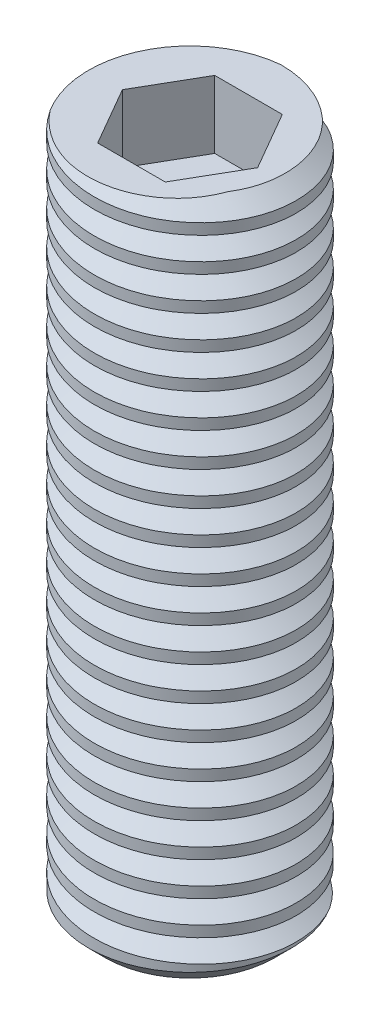
SolidWorks part; units mm, degrees
ref_plane "Alzado" through (0, 0, 0) normal (0, 0, 1) x (1, 0, 0)
ref_plane "Planta" through (0, 0, 0) normal (0, 1, 0) x (1, 0, 0)
ref_plane "Vista lateral" through (0, 0, 0) normal (1, 0, 0) x (0, 0, -1)
sketch "Croquis1" plane through (0, 0, 0) normal (0, 1, 0) x (1, 0, 0)
  circle A0 centre (0, 0) radius 1.5
  dimension "D1" = 3
extrude "Extruir1" add sketch "Croquis1" along normal blind 10
sketch "Croquis2" plane through (0, 0, 0) normal (0, 1, 0) x (1, 0, 0)
  circle A0 centre (0, 0) radius 1.5
  dimension "D1" = 3
curve "Hélice/Espiral1" pitch 0.5 height 21.5 turns 43
sketch "Croquis3" plane through (0, 0, 0) normal (1, 0, 0) x (0, 0, -1)
  line L0 (1.207, 0.3391) -> (1.64, 0.0891)
  line L1 (1.64, 0.0891) -> (1.7735, 0.0891)
  line L2 (1.7735, 0.0891) -> (1.7735, 0.5891)
  line L3 (1.7735, 0.5891) -> (1.64, 0.5891)
  line L4 (1.64, 0.5891) -> (1.207, 0.3391)
  line L5 (1.64, 0.5891) -> (1.64, 0.0891) construction
  line L6 (1.64, 0.3391) -> (1.207, 0.3391) construction
  dimension "D1" = 0.1334
  dimension "D2" = 0.5
  dimension "D3" = 0.5
sweep "Cortar-Barrer1" cut profiles "Croquis3" path "Hélice/Espiral1"
sketch "Croquis4" plane through (0, 10, 0) normal (0, 1, 0) x (1, 0, 0)
  line L1 (0.5, 0.866) -> (-0.5, 0.866)
  line L2 (-0.5, 0.866) -> (-1, 0)
  line L3 (-1, 0) -> (-0.5, -0.866)
  line L4 (-0.5, -0.866) -> (0.5, -0.866)
  line L5 (0.5, -0.866) -> (1, 0)
  line L6 (1, 0) -> (0.5, 0.866)
  circle A0 centre (0, 0) radius 0.866 construction
  dimension "D1" = 1
extrude "Extruir2" cut sketch "Croquis4" against normal blind 1
sketch "Croquis5" plane through (0, 0, 0) normal (0, -1, 0) x (1, 0, 0)
  line L1 (0.5, 0.866) -> (-0.5, 0.866)
  line L2 (-0.5, 0.866) -> (-1, 0)
  line L3 (-1, 0) -> (-0.5, -0.866)
  line L4 (-0.5, -0.866) -> (0.5, -0.866)
  line L5 (0.5, -0.866) -> (1, 0)
  line L6 (1, 0) -> (0.5, 0.866)
  circle A0 centre (0, 0) radius 0.866 construction
  dimension "D1" = 1
extrude "Extruir3" cut sketch "Croquis5" against normal blind 1
chamfer "Chaflán1" distance 0.25 angle 45 1 edges at (0, 0, 1.5)
